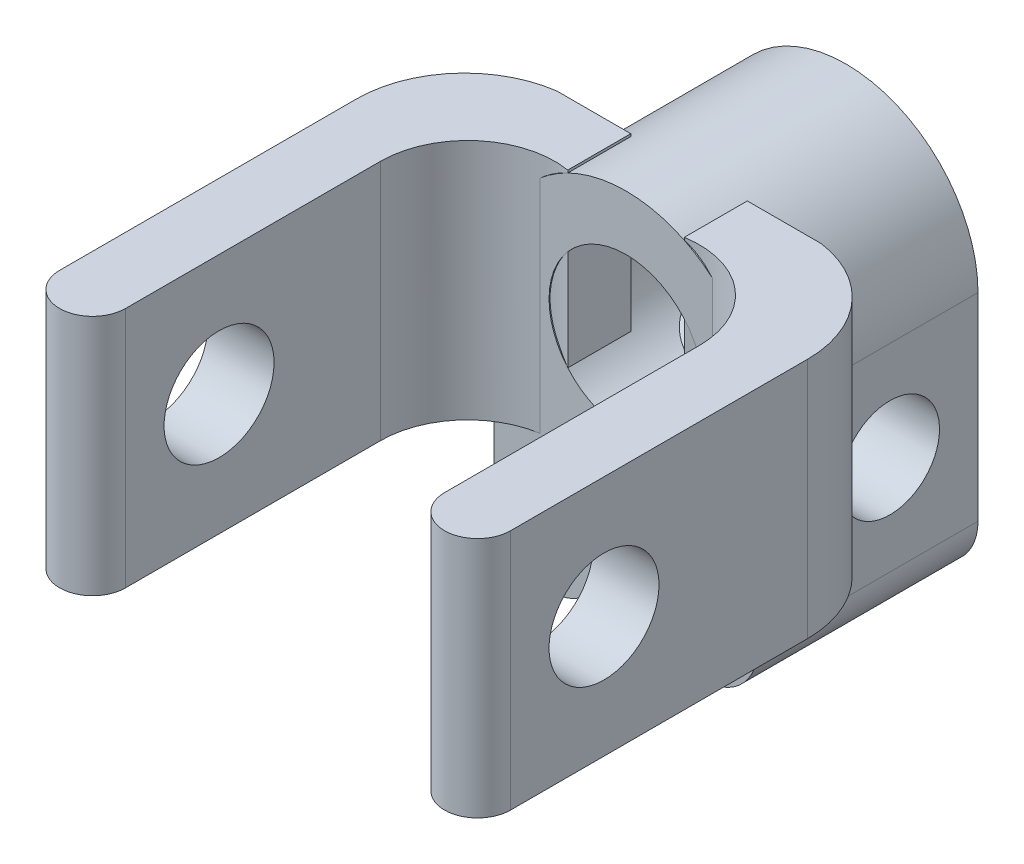
SolidWorks part; units mm, degrees
ref_plane "Front Plane" through (0, 0, 0) normal (0, 0, 1) x (1, 0, 0)
ref_plane "Top Plane" through (0, 0, 0) normal (0, 1, 0) x (1, 0, 0)
ref_plane "Right Plane" through (0, 0, 0) normal (1, 0, 0) x (0, 0, -1)
sketch "Sketch1" plane through (0, 0, 0) normal (0, 0, 1) x (1, 0, 0)
  line L0 (-12, 0) -> (12, 0) construction
  line L1 (-12, -18) -> (-12, 0)
  line L2 (12, 0) -> (12, -18)
  line L3 (-2, -18) -> (-2, -6.7082)
  line L4 (0, 0) -> (0, -38.2603) construction
  line L5 (2, -18) -> (2, -6.7082)
  arc A0 (2, -6.7082) -> (-2, -6.7082) centre (0, 0) ccw
  arc A1 (12, 0) -> (-12, 0) centre (0, 0) ccw
  arc A2 (-12, -18) -> (-2, -18) centre (-7, -18) ccw
  arc A3 (12, -18) -> (2, -18) centre (7, -18) cw
  point P6 (0, 0)
  dimension "D1" = 14
  dimension "D3" = 18
  dimension "D4" = 10
  dimension "D2" = 24
extrude "Boss-Extrude1" add sketch "Sketch1" along normal blind 20
sketch "Sketch2" plane through (0, 0, 0) normal (0, 1, 0) x (1, 0, 0)
  line L0 (0, 0) -> (0, -54) construction
  line L1 (-20.5, -51) -> (-20.5, -24)
  line L2 (-12, -20) -> (-12, 0) construction
  line L3 (-14.5, -51) -> (-14.5, -27.8281)
  line L4 (-12, -20) -> (12, -20) construction
  line L5 (21.6606, -54) -> (-21.6606, -54) construction
  line L6 (14.5, -51) -> (14.5, -27.8281)
  line L7 (20.5, -51) -> (20.5, -24)
  line L10 (-12, -14.2716) -> (-5.2969, -14.2716)
  line L11 (-5.2969, -14.2716) -> (-5.2969, -20)
  line L12 (12, -14.2716) -> (5.2969, -14.2716)
  line L13 (5.2969, -14.2716) -> (5.2969, -20)
  arc A0 (-20.5, -24) -> (-12, -14.2716) centre (-10.6829, -24) cw
  arc A1 (-20.5, -51) -> (-14.5, -51) centre (-17.5, -51) ccw
  arc A2 (-14.5, -27.8281) -> (-5.2969, -20) centre (-6.5692, -27.8281) cw
  arc A3 (14.5, -27.8281) -> (5.2969, -20) centre (6.5692, -27.8281) ccw
  arc A4 (20.5, -51) -> (14.5, -51) centre (17.5, -51) cw
  arc A5 (20.5, -24) -> (12, -14.2716) centre (10.6829, -24) ccw
  point P19 (0, -54)
  dimension "D2" = 6
  dimension "D4" = 27
  dimension "D1" = 54
  dimension "D3" = 41
extrude "Boss-Extrude2" add sketch "Sketch2" along normal blind 11 and the other way blind 11
sketch "Sketch3" plane through (0, 0, 0) normal (1, 0, 0) x (0, 0, -1)
  line L0 (0, 0) -> (-54, 0) construction
  line L1 (-54, 11) -> (-54, -11) construction
  line L2 (0, -18) -> (0, 0) construction
  line L3 (-20, -23) -> (0, -23) construction
  circle A0 centre (-42.5, 0) radius 5
  circle A1 centre (-8, -9) radius 4.5
  dimension "D1" = 10
  dimension "D3" = 9
  dimension "D2" = 11.5
  dimension "D4" = 8
  dimension "D5" = 14
extrude "Cut-Extrude1" cut sketch "Sketch3" against normal through all both and the other way through all
sketch3d "3DSketch1"
  line L0 (20.5, 0, 42.5) -> (-20.5, 0, 42.5) construction
  line L1 (14.5, 0, 42.5) -> (20.5, 0, 42.5) construction
  line L2 (0, 0, 42.5) -> (0, 0, 0) construction
  circle A0 centre (-20.5, 0, 42.5) radius 5 construction
  circle A1 centre (20.5, 0, 42.5) radius 5 construction
  point P4 (0, 0, 42.5)
  point P8 (-15.5, 0, 42.5)
  point P14 (25.5, 0, 42.5)
